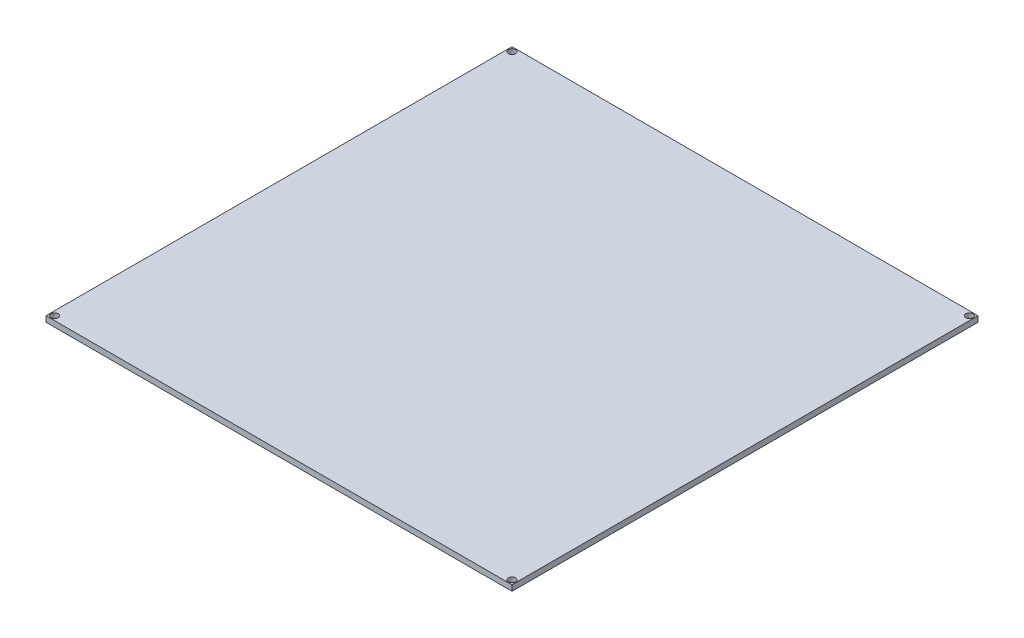
SolidWorks part; units mm, degrees
ref_plane "Front Plane" through (0, 0, 0) normal (0, 0, 1) x (1, 0, 0)
ref_plane "Top Plane" through (0, 0, 0) normal (0, 1, 0) x (1, 0, 0)
ref_plane "Right Plane" through (0, 0, 0) normal (1, 0, 0) x (0, 0, -1)
sketch "Sketch1" plane through (0, 0, 0) normal (0, 1, 0) x (1, 0, 0)
  line L1 (-176, 98.8696) -> (151, 98.8696)
  line L2 (-176, 98.8696) -> (-176, -228.1304)
  line L3 (-176, -228.1304) -> (151, -228.1304)
  line L4 (151, 98.8696) -> (151, -228.1304)
  circle A0 centre (-173, -225.1304) radius 2.5
  circle A1 centre (-173, 95.8696) radius 2.5
  circle A2 centre (148, 95.8696) radius 2.5
  circle A3 centre (148, -225.1304) radius 2.5
  point P14 (-174.4914, 98.9164)
  dimension "D3" = 3
  dimension "D5" = 3
  dimension "D1" = 327
  dimension "D2" = 327
  dimension "D4" = 3
  dimension "D6" = 3
  dimension "D7" = 3
  dimension "D8" = 3
  dimension "D9" = 3
  dimension "D10" = 3
extrude "Boss-Extrude1" add sketch "Sketch1" along normal blind 4
